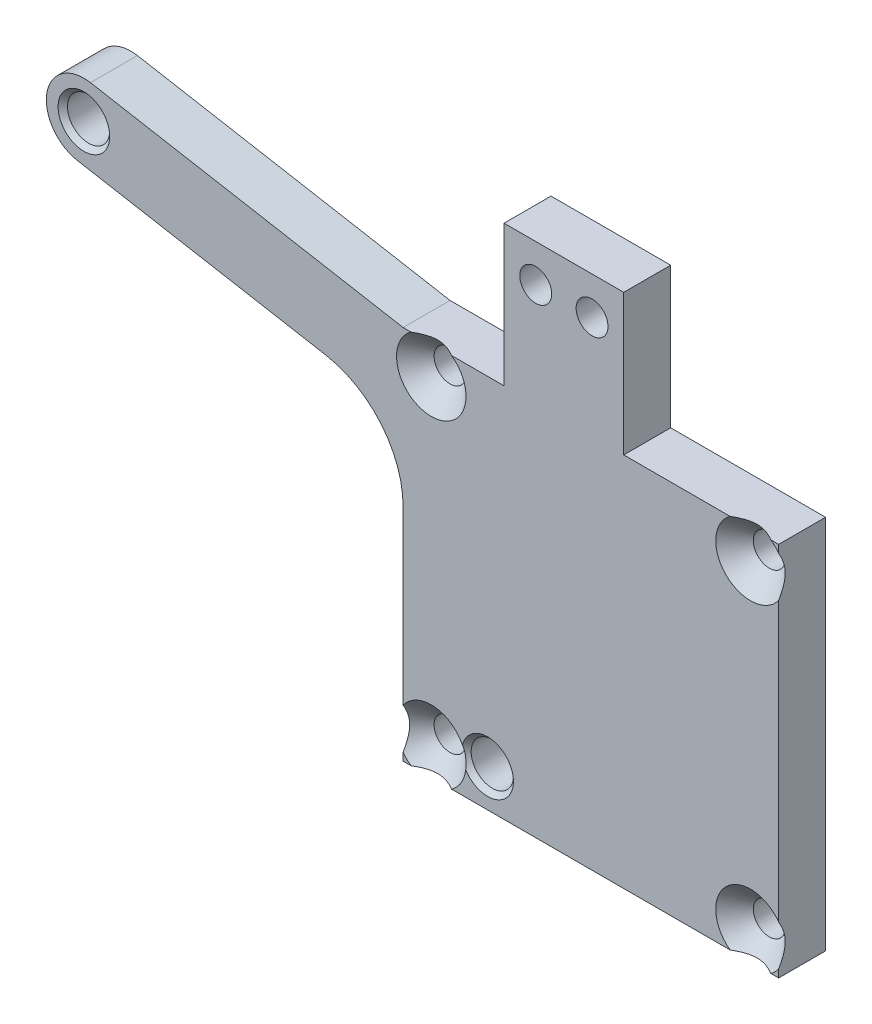
SolidWorks part; units mm, degrees
ref_plane "Front Plane" through (0, 0, 0) normal (0, 0, 1) x (1, 0, 0)
ref_plane "Top Plane" through (0, 0, 0) normal (0, 1, 0) x (1, 0, 0)
ref_plane "Right Plane" through (0, 0, 0) normal (1, 0, 0) x (0, 0, -1)
sketch "Sketch1" plane through (0, 0, 0) normal (0, 0, 1) x (1, 0, 0)
  line L0 (3.5, 20) -> (3.5, 35)
  line L1 (20, 20) -> (3.5, 20)
  line L2 (20, 20) -> (20, -20)
  line L3 (20, -20) -> (-20, -20)
  line L4 (-20, 3.4993) -> (-20, -20)
  line L5 (20, 20) -> (-20, -20) construction
  line L6 (20, -20) -> (-20, 20) construction
  line L7 (17, 17) -> (-17, 17) construction
  line L8 (17, 17) -> (17, -17) construction
  line L9 (17, -17) -> (-17, -17) construction
  line L10 (-17, 17) -> (-17, -17) construction
  line L11 (17, 17) -> (-17, -17) construction
  line L12 (17, -17) -> (-17, 17) construction
  line L13 (3.5, 35) -> (-9.25, 35)
  line L14 (-9.25, 35) -> (-9.25, 20)
  line L15 (-9.25, 20) -> (-20, 20)
  line L16 (-9.25, 31) -> (3.5, 31) construction
  line L17 (-53.2978, 25.9379) -> (-20, 20)
  line L18 (-54.7022, 18.0621) -> (-28.2444, 13.344)
  line L19 (-20, 3.4993) -> (-20, 20) construction
  circle A0 centre (-17, 17) radius 1.7
  circle A1 centre (17, 17) radius 1.7
  circle A2 centre (17, -17) radius 1.7
  circle A3 centre (-17, -17) radius 1.7
  circle A4 centre (-5.875, 31) radius 1.7
  circle A5 centre (0.125, 31) radius 1.7
  circle A6 centre (-11, -16) radius 2.25
  circle A7 centre (-54, 22) radius 2.25
  arc A8 (-53.2978, 25.9379) -> (-54.7022, 18.0621) centre (-54, 22) ccw
  arc A9 (-20, 3.4993) -> (-28.2444, 13.344) centre (-30, 3.4993) ccw
  point P0 (0, 0)
  point P5 (0, 0)
  point P25 (-2.875, 31)
  point P28 (-54, 22)
  dimension "D4" = 3.4
  dimension "D5" = 3.4
  dimension "D6" = 3.4
  dimension "D7" = 3.4
  dimension "D12" = 3
  dimension "D14" = 3.4
  dimension "D15" = 3.4
  dimension "D16" = 9
  dimension "D17" = 4
  dimension "D18" = 4.5
  dimension "D21" = 4.5
  dimension "D22" = 8
  dimension "D23" = 10
  dimension "D2" = 40
  dimension "D3" = 34
  dimension "D8" = 16.5
  dimension "D9" = 15
  dimension "D10" = 12.75
  dimension "D11" = 4
  dimension "D13" = 3
  dimension "D19" = 34
  dimension "D20" = 2
  dimension "D24" = 34
  dimension "D25" = 3
extrude "Boss-Extrude1" add sketch "Sketch1" along normal blind 5
chamfer "Chamfer1" distance 2 angle 45 4 edges at (18.7, 17, 5) (18.7, -17, 5) (-15.3, -17, 5) (-15.3, 17, 5)
chamfer "Chamfer2" distance 0.5 angle 45 2 edges at (-8.75, -16, 5) (-51.75, 22, 5)
